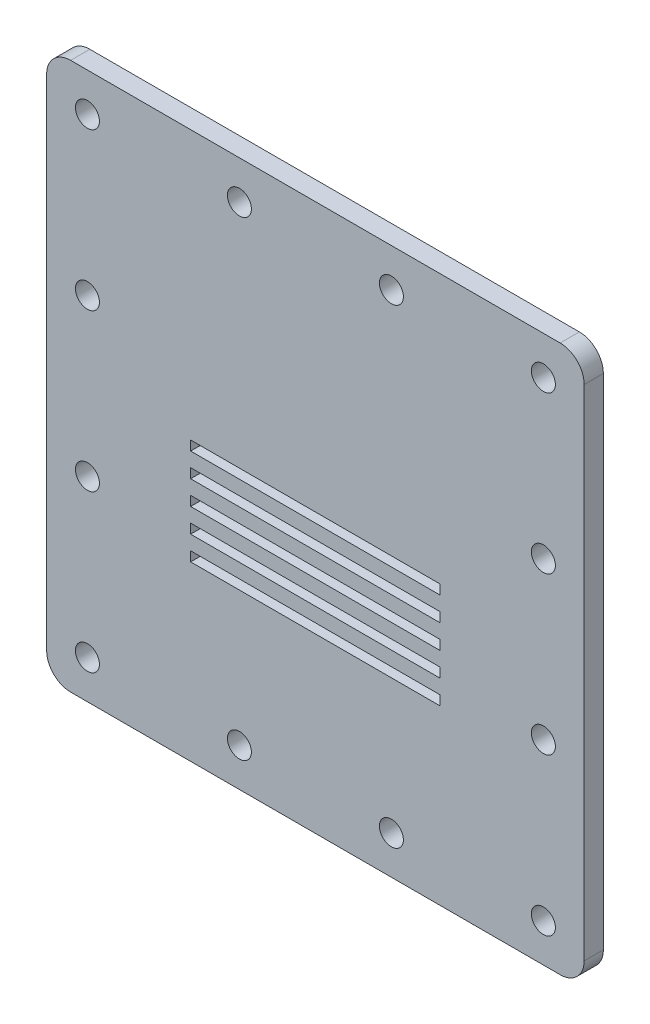
SolidWorks part; units mm, degrees
ref_plane "Front Plane" through (0, 0, 0) normal (0, 0, 1) x (1, 0, 0)
ref_plane "Top Plane" through (0, 0, 0) normal (0, 1, 0) x (1, 0, 0)
ref_plane "Right Plane" through (0, 0, 0) normal (1, 0, 0) x (0, 0, -1)
sketch "Sketch1" plane through (0, 0, 0) normal (0, 0, 1) x (1, 0, 0)
  line L1 (-19, -19.5) -> (19, -19.5) construction
  line L2 (-19, -19.5) -> (-19, 19.5) construction
  line L3 (-19, 19.5) -> (19, 19.5) construction
  line L4 (19, -19.5) -> (19, 19.5) construction
  line L5 (-19, -19.5) -> (19, 19.5) construction
  line L6 (-19, 19.5) -> (19, -19.5) construction
  line L7 (-28, -28.5) -> (28, -28.5)
  line L8 (-28, -28.5) -> (-28, 28.5)
  line L9 (-28, 28.5) -> (28, 28.5)
  line L10 (28, -28.5) -> (28, 28.5)
  line L11 (-28, -28.5) -> (28, 28.5) construction
  line L12 (-28, 28.5) -> (28, -28.5) construction
  point P0 (0, 0)
  point P6 (0, 0)
  dimension "D1" = 38
  dimension "D2" = 39
  dimension "D3" = 9
  dimension "D4" = 9
extrude "Boss-Extrude1" add sketch "Sketch1" along normal blind 2
fillet "Fillet1" radius 2.5 4 edges at (-28, -28.5, 1) (28, -28.5, 1) (-28, 28.5, 1) (28, 28.5, 1)
sketch "Sketch2" plane through (0, 0, 2) normal (0, 0, 1) x (1, 0, 0)
  line L0 (-19, -19.5) -> (-19, 19.5) construction
  line L1 (-23.75, -24.5) -> (23.75, -24.5) construction
  line L2 (-23.75, -24.5) -> (-23.75, 24.5) construction
  line L3 (-23.75, 24.5) -> (23.75, 24.5) construction
  line L4 (23.75, -24.5) -> (23.75, 24.5) construction
  line L5 (-23.75, -24.5) -> (23.75, 24.5) construction
  line L6 (-23.75, 24.5) -> (23.75, -24.5) construction
  line L7 (-19, 19.5) -> (19, 19.5) construction
  circle A0 centre (-23.75, 24.5) radius 1.25
  circle A1 centre (-7.9167, 24.5) radius 1.25
  circle A2 centre (7.9167, 24.5) radius 1.25
  circle A3 centre (23.75, 24.5) radius 1.25
  circle A6 centre (23.75, 8.1667) radius 1.25
  circle A9 centre (23.75, -8.1667) radius 1.25
  circle A10 centre (-7.9167, -24.5) radius 1.25
  circle A11 centre (7.9167, -24.5) radius 1.25
  circle A12 centre (23.75, -24.5) radius 1.25
  circle A13 centre (-23.75, 8.1667) radius 1.25
  circle A14 centre (-23.75, -8.1667) radius 1.25
  circle A15 centre (-23.75, -24.5) radius 1.25
  circle A16 centre (-7.9167, 8.1667) radius 1.25 [skipped]
  circle A17 centre (7.9167, 8.1667) radius 1.25 [skipped]
  circle A18 centre (7.9167, -8.1667) radius 1.25 [skipped]
  circle A19 centre (-7.9167, -8.1667) radius 1.25 [skipped]
  point P0 (0, 0)
  dimension "D3" = 2.5
  dimension "D1" = 4.75
  dimension "D2" = 5
  dimension "D5" = 4
  dimension "D4" = 4
extrude "Cut-Extrude1" cut sketch "Sketch2" against normal up to surface (2 mm away) up to face at (0, 0, 0)
sketch "Sketch3" plane through (0, 0, 2) normal (0, 0, 1) x (1, 0, 0)
  line L0 (-28, -28.5) -> (-28, 28.5) construction
  line L1 (-13, 0.5) -> (13, 0.5)
  line L2 (-13, 0.5) -> (-13, -0.5)
  line L3 (-13, -0.5) -> (13, -0.5)
  line L4 (13, 0.5) -> (13, -0.5)
  line L5 (-13, 0.5) -> (13, -0.5) construction
  line L6 (-13, -0.5) -> (13, 0.5) construction
  line L7 (-13, -2) -> (-13, -3)
  line L8 (-13, -2) -> (13, -2)
  line L9 (13, -2) -> (13, -3)
  line L10 (-13, -3) -> (13, -3)
  line L11 (-13, -4.5) -> (-13, -5.5)
  line L12 (-13, -4.5) -> (13, -4.5)
  line L13 (13, -4.5) -> (13, -5.5)
  line L14 (-13, -5.5) -> (13, -5.5)
  line L15 (-13, -7) -> (-13, -8)
  line L16 (-13, -7) -> (13, -7)
  line L17 (13, -7) -> (13, -8)
  line L18 (-13, -8) -> (13, -8)
  line L19 (-13, -9.5) -> (-13, -10.5)
  line L20 (-13, -9.5) -> (13, -9.5)
  line L21 (13, -9.5) -> (13, -10.5)
  line L22 (-13, -10.5) -> (13, -10.5)
  point P0 (0, 0)
  dimension "D1" = 1
  dimension "D2" = 15
  dimension "D4" = 2.5
  dimension "D3" = 5
extrude "Cut-Extrude2" cut sketch "Sketch3" against normal up to surface (2 mm away) up to face at (-25, -24.5, 0)
equation "\"case_width\"=38.00"
equation "\"D1@Sketch1\"=\"case_width\""
